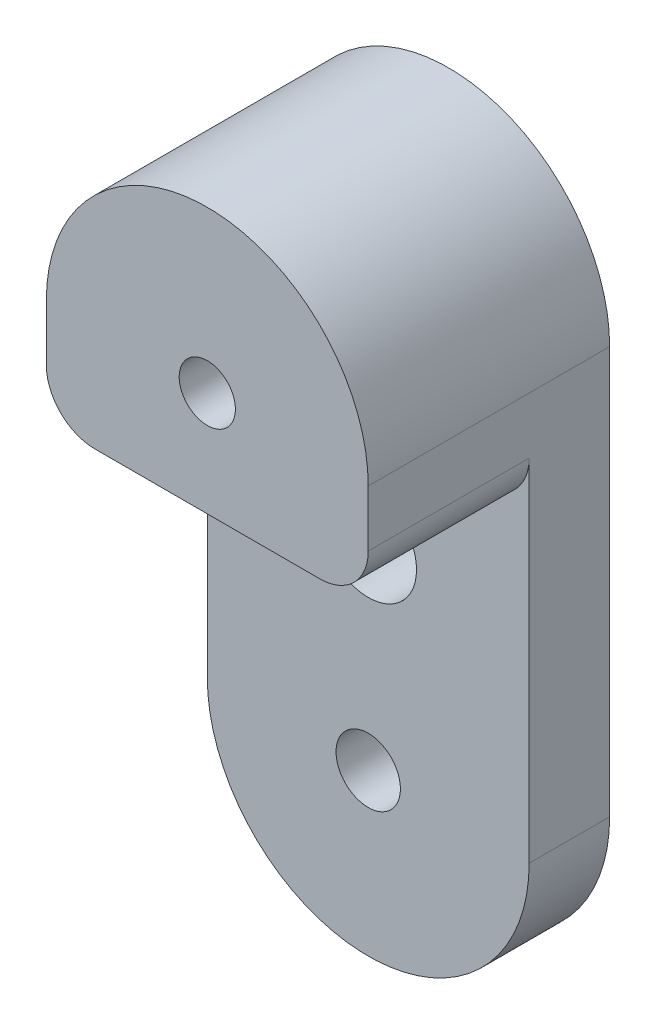
SolidWorks part; units mm, degrees
ref_plane "Front Plane" through (0, 0, 0) normal (0, 0, 1) x (1, 0, 0)
ref_plane "Top Plane" through (0, 0, 0) normal (0, 1, 0) x (1, 0, 0)
ref_plane "Right Plane" through (0, 0, 0) normal (1, 0, 0) x (0, 0, -1)
sketch "Sketch1" plane through (0, 0, 0) normal (0, 0, 1) x (1, 0, 0)
  line L0 (0, 0) -> (0, -25.3) construction
  line L1 (10, 0) -> (10, -25.3)
  line L2 (-10, 0) -> (-10, -25.3)
  line L3 (-10, -6.5) -> (10, -6.5)
  circle A0 centre (0, 0) radius 1.7462
  circle A1 centre (0, -13) radius 3
  circle A2 centre (0, -25.3) radius 2
  arc A3 (10, 0) -> (-10, 0) centre (0, 0) ccw
  arc A4 (-10, -25.3) -> (10, -25.3) centre (0, -25.3) ccw
  point P7 (0, -12.65)
  dimension "D1" = 4
  dimension "D2" = 6
  dimension "D3" = 3.4925
  dimension "D4" = 13
  dimension "D5" = 7.3
  dimension "D6" = 20
  dimension "D7" = 13
  dimension "D8" = 6.5
extrude "Boss-Extrude1" add sketch "Sketch1" along normal blind 5 contours L2 A4 L1 L3 A1 A2 region at (0, -20.1806, 0)
extrude "Boss-Extrude2" add sketch "Sketch1<3>" along normal blind 15 contours A0 L3 L1 A3 L2 region at (9.7407, -3.25, 0)
sketch "Sketch1<3>" plane through (0, 0, 0) normal (0, 0, 1) x (1, 0, 0) same geometry as "Sketch1"
fillet "Fillet1" radius 3 2 edges at (10, -6.5, 10) (-10, -6.5, 10)
equation "\"D8@Sketch1\"=\"D7@Sketch1\"/2"
equation "\"D3@Sketch1\"=0.125*25.4*1.1"
